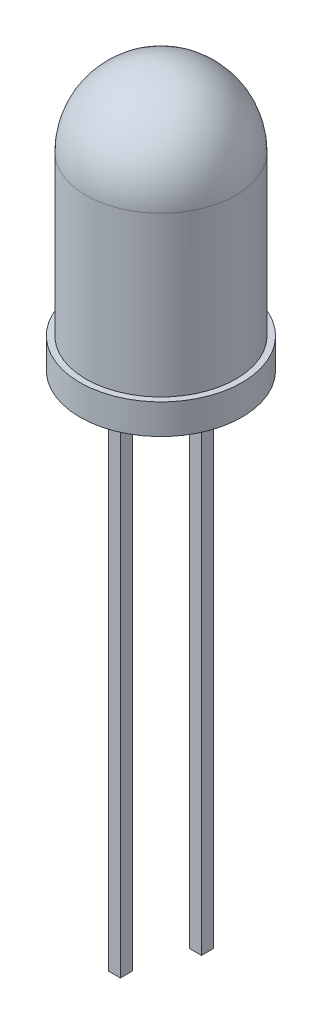
SolidWorks part; units mm, degrees
ref_plane "Front Plane" through (0, 0, 0) normal (0, 0, 1) x (1, 0, 0)
ref_plane "Top Plane" through (0, 0, 0) normal (0, 1, 0) x (1, 0, 0)
ref_plane "Right Plane" through (0, 0, 0) normal (1, 0, 0) x (0, 0, -1)
sketch "Sketch1" plane through (0, 0, 0) normal (0, 0, 1) x (1, 0, 0)
  line L0 (0, 0) -> (2.7, 0)
  line L1 (2.7, 0) -> (2.7, 1)
  line L2 (2.7, 1) -> (2.5, 1)
  line L3 (2.5, 1) -> (2.5, 6.3)
  line L4 (0, 8.8) -> (0, 0)
  arc A0 (2.5, 6.3) -> (0, 8.8) centre (0, 6.3) ccw
  dimension "D1" = 2.7
  dimension "D2" = 1
  dimension "D3" = 2.5
  dimension "D4" = 8.8
revolve "Revolve1" add sketch "Sketch1" angle 360 about L4
sketch "Sketch2" plane through (0, 0, 0) normal (0, 0, 1) x (1, 0, 0)
  line L0 (-2.7, 0) -> (2.7, 0) construction
  line L1 (1.15, 0) -> (1.55, 0)
  line L2 (1.15, 0) -> (1.15, -16)
  line L3 (1.15, -16) -> (1.55, -16)
  line L4 (1.55, 0) -> (1.55, -16)
  line L5 (1.15, 0) -> (-1.15, 0) construction
  line L6 (-1.55, 0) -> (-1.15, 0)
  line L7 (-1.55, 0) -> (-1.55, -18)
  line L8 (-1.55, -18) -> (-1.15, -18)
  line L9 (-1.15, 0) -> (-1.15, -18)
  point P10 (0, 0)
  dimension "D1" = 0.4
  dimension "D2" = 3.1
  dimension "D3" = 18
  dimension "D4" = 16
extrude "Boss-Extrude1" add sketch "Sketch2" along normal blind 0.2 and the other way blind 0.2
ref_axis "Beam" through (0, 183.6664, 0) along (0, -1, 0)
